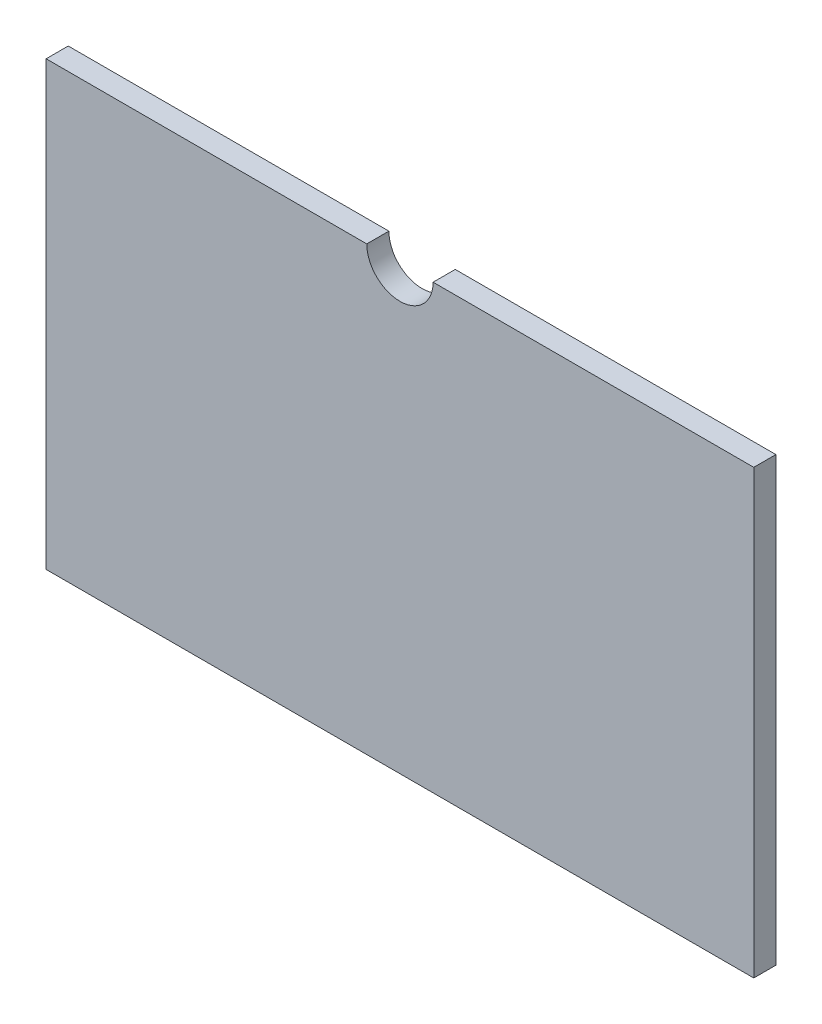
SolidWorks part; units mm, degrees
ref_plane "Front Plane" through (0, 0, 0) normal (0, 0, 1) x (1, 0, 0)
ref_plane "Top Plane" through (0, 0, 0) normal (0, 1, 0) x (1, 0, 0)
ref_plane "Right Plane" through (0, 0, 0) normal (1, 0, 0) x (0, 0, -1)
sketch "Sketch1" plane through (0, 0, 0) normal (0, 0, 1) x (1, 0, 0)
  line L0 (0, 0) -> (0, 100) construction
  line L1 (-160, 100) -> (-15, 100)
  line L2 (-160, 100) -> (-160, -100)
  line L3 (-160, -100) -> (160, -100)
  line L4 (160, 100) -> (160, -100)
  line L5 (-160, 0) -> (160, 0) construction
  line L6 (15, 100) -> (160, 100)
  line L7 (-15, 100) -> (15, 100) construction
  arc A0 (15, 100) -> (-15, 100) centre (0, 100) cw
  point P10 (0, 111.2173)
  point P12 (0, 100)
  dimension "D3" = 15
  dimension "D1" = 320
  dimension "D2" = 200
  dimension "D4" = 160
extrude "Bottom Center Casing" add sketch "Sketch1" along normal blind 10
sketch "Sketch2" plane through (0, 0, 10) normal (0, 0, 1) x (1, 0, 0)
  line L0 (-15, 100) -> (-160, 100) construction
  line L1 (160, 100) -> (15, 100) construction
  point P0 (-87.5, 100)
  point P3 (-87.5, 100)
  point P4 (87.5, 100)
  point P7 (87.5, 100)
